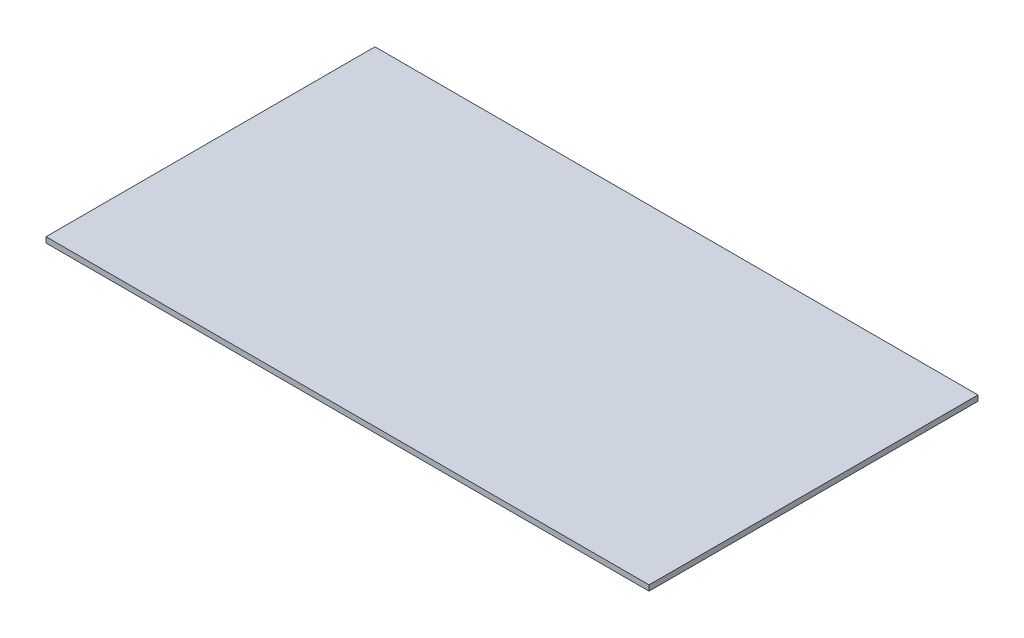
SolidWorks part; units mm, degrees
ref_plane "Front Plane" through (0, 0, 0) normal (0, 0, 1) x (1, 0, 0)
ref_plane "Top Plane" through (0, 0, 0) normal (0, 1, 0) x (1, 0, 0)
ref_plane "Right Plane" through (0, 0, 0) normal (1, 0, 0) x (0, 0, -1)
sketch "Sketch1" plane through (0, 0, 0) normal (0, 1, 0) x (1, 0, 0)
  line L1 (-245.6916, 157.385) -> (33.7084, 157.385)
  line L2 (-245.6916, 157.385) -> (-245.6916, 4.985)
  line L3 (-245.6916, 4.985) -> (33.7084, 4.985)
  line L4 (33.7084, 157.385) -> (33.7084, 4.985)
  dimension "D1" = 152.4
  dimension "D2" = 279.4
extrude "Boss-Extrude1" add sketch "Sketch1" along normal blind 2.54 contours L2 L3 L4 L1
